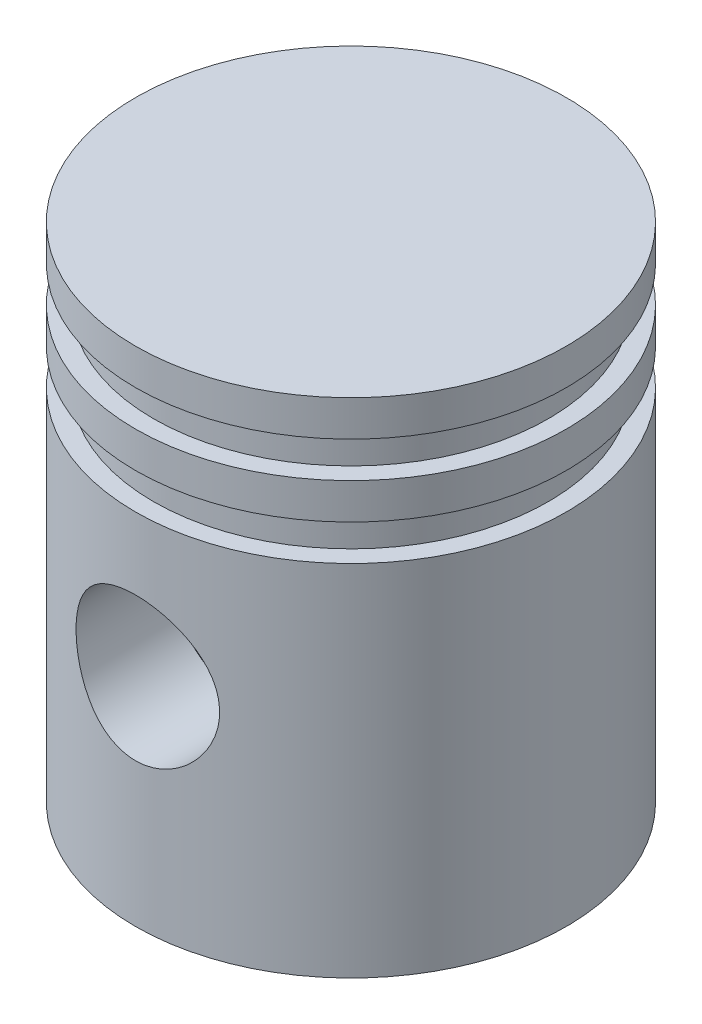
SolidWorks part; units mm, degrees
material "AISI 1020"
ref_plane "Front Plane" through (0, 0, 0) normal (0, 0, 1) x (1, 0, 0)
ref_plane "Top Plane" through (0, 0, 0) normal (0, 1, 0) x (1, 0, 0)
ref_plane "Right Plane" through (0, 0, 0) normal (1, 0, 0) x (0, 0, -1)
sketch "Sketch1" plane through (0, 0, 0) normal (0, 1, 0) x (1, 0, 0)
  circle A0 centre (0, 0) radius 15
  dimension "D1" = 30
extrude "Boss-Extrude1" add sketch "Sketch1" against normal blind 35
sketch "Sketch2" plane through (0, 0, 0) normal (0, 0, 1) x (1, 0, 0)
  line L0 (-15, 0) -> (-15, -35) construction
  line L1 (-15, -2.5) -> (-13.75, -2.5)
  line L2 (-15, -2.5) -> (-15, -5)
  line L3 (-15, -5) -> (-13.75, -5)
  line L4 (-13.75, -2.5) -> (-13.75, -5)
  line L6 (-15, -7.5) -> (-13.75, -7.5)
  line L7 (-15, -7.5) -> (-15, -10)
  line L8 (-15, -10) -> (-13.75, -10)
  line L9 (-13.75, -7.5) -> (-13.75, -10)
  dimension "D1" = 2.5
  dimension "D2" = 2.5
  dimension "D3" = 2.5
  dimension "D4" = 2.5
  dimension "D5" = 1.25
  dimension "D6" = 1.25
revolve "Cut-Revolve3" cut sketch "Sketch2" angle 360 about L0
sketch "Sketch4" plane through (0, 0, 0) normal (0, 0, 1) x (1, 0, 0)
  circle A0 centre (0, -20) radius 5
  dimension "D1" = 15
extrude "Cut-Extrude1" cut sketch "Sketch4" against normal mid plane 30 contours A0
sketch "Sketch5" plane through (0, -35, 0) normal (0, -1, 0) x (-1, 0, 0)
  circle A0 centre (0, 0) radius 10.25
extrude "Cut-Extrude2" cut sketch "Sketch5" against normal blind 25
sketch "Sketch6" plane through (0, 0, 0) normal (0, 0, 1) x (1, 0, 0)
  circle A0 centre (0, -20) radius 5
  circle A1 centre (0, -20) radius 6.5
extrude "Boss-Extrude2" add sketch "Sketch6" along normal mid plane 25 contours A0 | A1 A0
ref_plane "Plane1" through (6.5, 0, 0) normal (1, 0, 0) x (0, 0, -1)
sketch "Sketch9" plane through (6.5, 0, 0) normal (1, 0, 0) x (0, 0, -1)
  line L0 (0, -35) -> (0, -10) construction
  line L1 (-7.5, -27.6539) -> (7.5, -27.6539)
  line L2 (-7.5, -27.6539) -> (-7.5, -12.6539)
  line L3 (-7.5, -12.6539) -> (7.5, -12.6539)
  line L4 (7.5, -27.6539) -> (7.5, -12.6539)
  line L5 (-7.5, -27.6539) -> (7.5, -12.6539) construction
  line L6 (-7.5, -12.6539) -> (7.5, -27.6539) construction
  point P0 (0, -20.1539)
  dimension "D1" = 15
  dimension "D2" = 15
extrude "Cut-Extrude4" cut sketch "Sketch9" against normal blind 13 contours L2 L1 L4 L3
